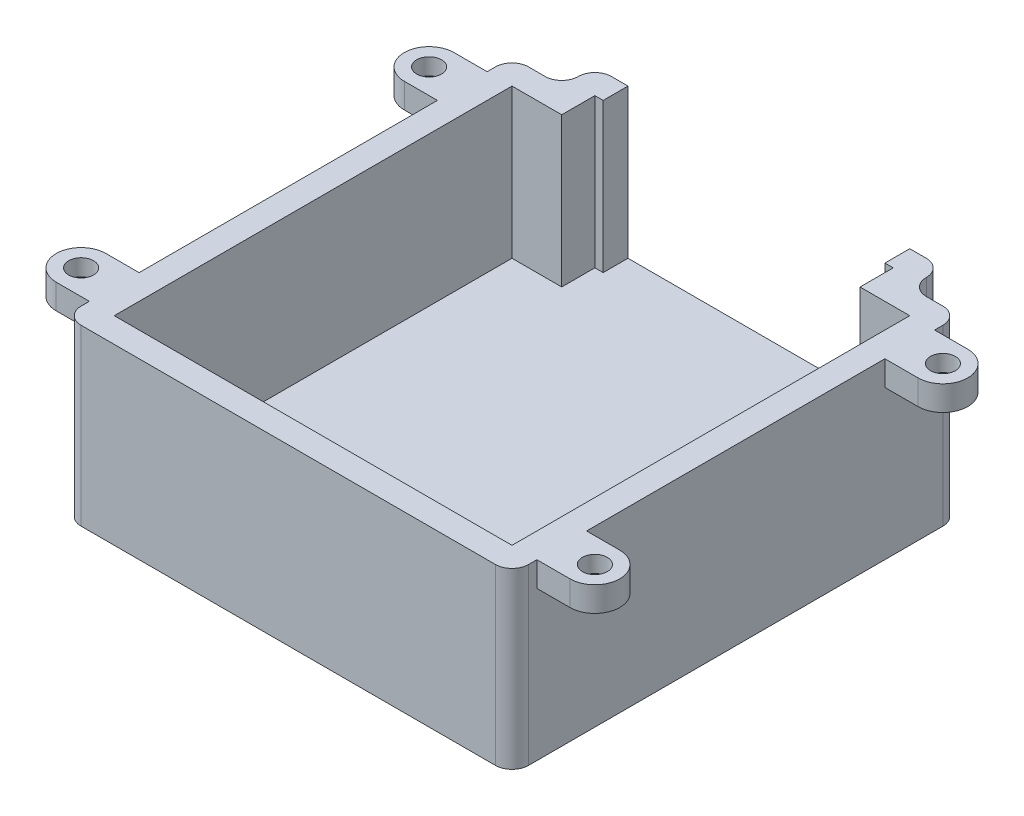
SolidWorks part; units mm, degrees
material "PLA Infill"
ref_plane "Front Plane" through (0, 0, 0) normal (0, 0, 1) x (1, 0, 0)
ref_plane "Top Plane" through (0, 0, 0) normal (0, 1, 0) x (1, 0, 0)
ref_plane "Right Plane" through (0, 0, 0) normal (1, 0, 0) x (0, 0, -1)
sketch "Sketch1" plane through (0, 0, 0) normal (0, 1, 0) x (1, 0, 0)
  line L0 (0, 54) -> (0, 0)
  line L1 (0, 0) -> (54, 0)
  line L2 (0, 0) -> (0, 58) construction
  line L3 (0, 58) -> (54, 58) construction
  line L4 (54, 0) -> (54, 58) construction
  line L5 (0, 58) -> (6, 58) construction
  line L6 (0, 58) -> (0, 54) construction
  line L7 (0, 54) -> (6, 54)
  line L8 (6, 58) -> (6, 54)
  line L9 (54, 58) -> (48, 58) construction
  line L10 (54, 58) -> (54, 54) construction
  line L11 (54, 54) -> (48, 54)
  line L12 (48, 58) -> (48, 54)
  line L13 (6, 58) -> (48, 58)
  line L14 (54, 54) -> (54, 0)
  dimension "D1" = 54
  dimension "D2" = 58
  dimension "D3" = 6
  dimension "D4" = 4
extrude "Boss-Extrude1" add sketch "Sketch1" along normal blind 21
shell "Shell2" thickness 3 removed face at (27, 21, -41.5)
sketch "Sketch2" plane through (0, 0, -58) normal (0, 0, -1) x (-1, 0, 0)
  line L1 (-44, 3) -> (-10, 3)
  line L2 (-44, 3) -> (-44, 21)
  line L3 (-44, 21) -> (-10, 21)
  line L4 (-10, 3) -> (-10, 21)
  line L7 (-27, 0) -> (-27, 21) construction
  line L9 (-48, 21) -> (-6, 21) construction
  line L10 (-48, 0) -> (-6, 0) construction
  point P10 (-27, 3)
  dimension "D1" = 18
  dimension "D2" = 34
extrude "Cut-Extrude1" cut sketch "Sketch2" against normal up to surface (3 mm away) up to face at (27, 12, -55)
fillet "Fillet2" radius 2 8 edges at (6, 10.5, -58) (6, 10.5, -54) (0, 10.5, -54) (0, 10.5, 0) (54, 10.5, 0) (48, 10.5, -54) (48, 10.5, -58) (54, 10.5, -54)
sketch "Sketch4" plane through (0, 21, 0) normal (0, 1, 0) x (1, 0, 0)
  line L0 (27, -1000) -> (27, 49000) construction
  line L1 (2, 0) -> (52, 0) construction
  line L2 (0, 52) -> (0, 2) construction
  line L7 (-7, 48) -> (0, 48) construction
  line L8 (0, 51) -> (-7, 51) construction
  line L9 (0, 51) -> (0, 45)
  line L10 (0, 45) -> (-7, 45) construction
  line L11 (-7, 51) -> (-7, 45) construction
  line L12 (-4, 51) -> (0, 51)
  line L13 (-4, 45) -> (0, 45)
  line L14 (-1000, 27) -> (49000, 27) construction
  line L15 (-4, 3) -> (0, 3)
  line L16 (0, 3) -> (0, 9)
  line L17 (-4, 9) -> (0, 9)
  line L18 (58, 9) -> (54, 9)
  line L19 (54, 3) -> (54, 9)
  line L20 (58, 3) -> (54, 3)
  line L21 (58, 51) -> (54, 51)
  line L22 (54, 51) -> (54, 45)
  line L23 (58, 45) -> (54, 45)
  circle A0 centre (-4, 48) radius 1.5
  arc A1 (-4, 45) -> (-4, 51) centre (-4, 48) cw
  circle A2 centre (-4, 6) radius 1.5
  arc A3 (-4, 9) -> (-4, 3) centre (-4, 6) ccw
  arc A4 (58, 9) -> (58, 3) centre (58, 6) cw
  circle A5 centre (58, 6) radius 1.5
  circle A6 centre (58, 48) radius 1.5
  arc A7 (58, 45) -> (58, 51) centre (58, 48) ccw
  point P5 (27, 0)
  point P23 (0, 27)
  dimension "D1" = 3
  dimension "D2" = 6
  dimension "D3" = 48
  dimension "D4" = 4
extrude "Boss-Extrude2" add sketch "Sketch4" against normal blind 3
chamfer "Chamfer1" distance 1 angle 45 4 edges at (-4, 18, -46.5) (-4, 18, -7.5) (58, 18, -4.5) (58, 18, -49.5)
